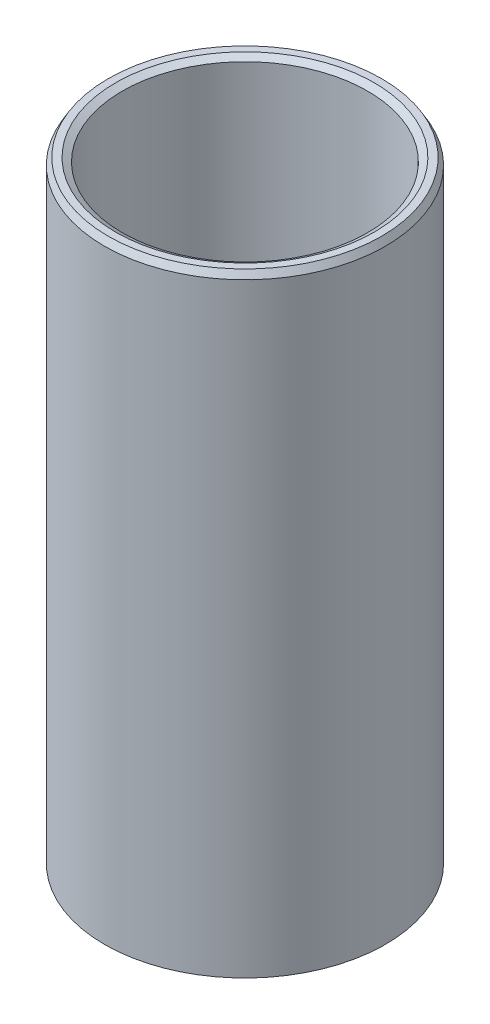
SolidWorks part; units mm, degrees
ref_plane "Front Plane" through (0, 0, 0) normal (0, 0, 1) x (1, 0, 0)
ref_plane "Top Plane" through (0, 0, 0) normal (0, 1, 0) x (1, 0, 0)
ref_plane "Right Plane" through (0, 0, 0) normal (1, 0, 0) x (0, 0, -1)
sketch "Sketch1" plane through (0, 0, 0) normal (0, 1, 0) x (1, 0, 0)
  circle A0 centre (0, 0) radius 57.5
  dimension "SLEEVE_OD" = 115
extrude "Boss-Extrude1" add sketch "Sketch1" along normal blind 251.8452
sketch "Sketch2" plane through (0, 0, 0) normal (0, 1, 0) x (1, 0, 0)
  circle A0 centre (0, 0) radius 50.2245
  dimension "BORE_D" = 100.449
extrude "Cut-Extrude1" cut sketch "Sketch2" along normal through all
chamfer "Chamfer1" distance 2.731 angle 30 4 edges at (0, 251.8452, 50.2245) (0, 0, 50.2245) (0, 0, 57.5) (0, 251.8452, 57.5) first distance on face at (0, 251.8452, 50.2245) first distance on face at (0, 0, 50.2245) first distance on face at (0, 251.8452, 57.5)
